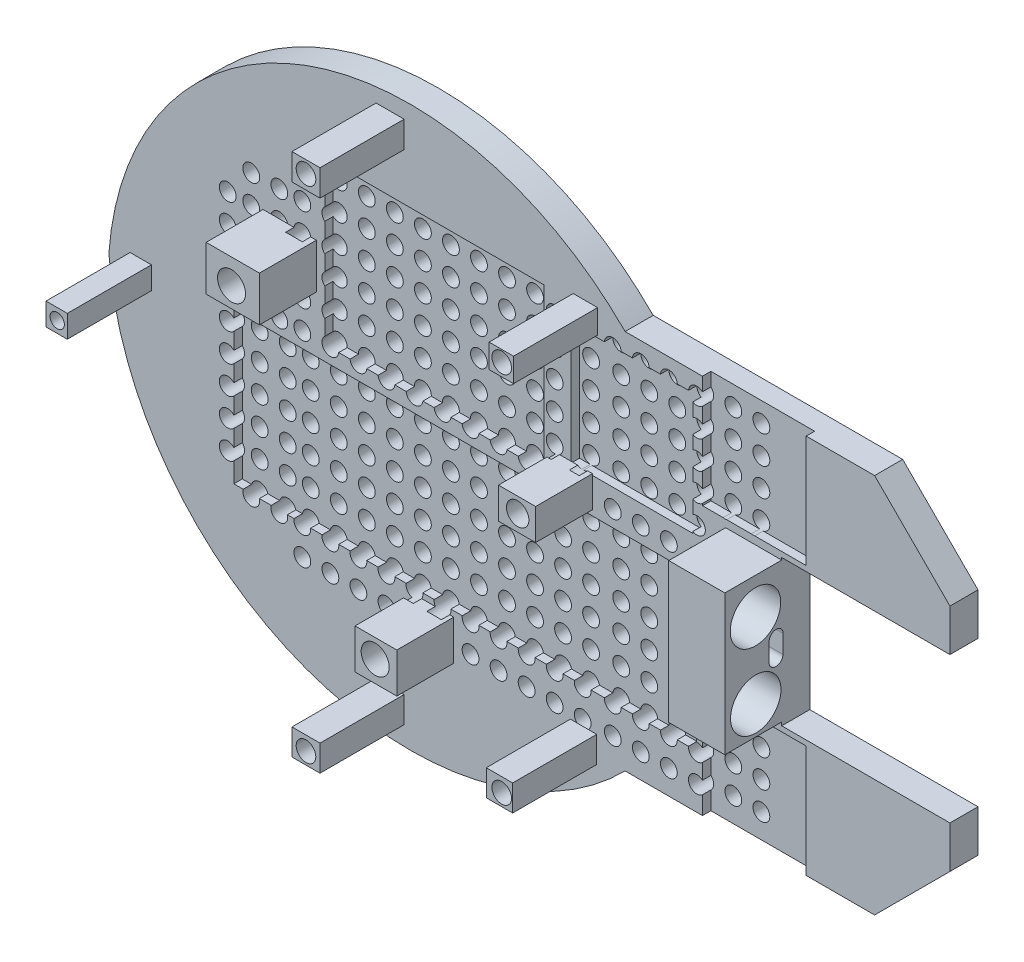
SolidWorks part; units mm, degrees
ref_plane "Front Plane" through (0, 0, 0) normal (0, 0, 1) x (1, 0, 0)
ref_plane "Top Plane" through (0, 0, 0) normal (0, 1, 0) x (1, 0, 0)
ref_plane "Right Plane" through (0, 0, 0) normal (1, 0, 0) x (0, 0, -1)
sketch "Sketch1" plane through (0, 0, 0) normal (0, 0, 1) x (1, 0, 0)
  line L1 (0, 0) -> (0, -26)
  line L2 (0, 26) -> (60, 26)
  line L3 (0, -26) -> (60, -26)
  line L4 (60, 26) -> (60, 41)
  line L5 (60, -26) -> (60, -41)
  line L6 (60, 41) -> (33.1299, 67.8701)
  line L7 (33.1299, 67.8701) -> (-55.8501, 67.8701)
  line L8 (60, -41) -> (33.1299, -67.8701)
  line L9 (33.1299, -67.8701) -> (-55.8501, -67.8701)
  line L10 (-55.8501, 67.8701) -> (-55.8501, 145.9436) construction
  line L11 (-55.8501, 145.9436) -> (-55.8501, -286.005) construction
  line L22 (0, 26) -> (0, 0)
  line L24 (-132.4482, 99.7954) -> (-270.7239, 99.7954) construction
  line L25 (-132.4482, 8.0579) -> (-132.4482, 125.9405) construction
  line L26 (-132.4482, -8.0579) -> (-132.4482, -125.1714) construction
  line L27 (-132.4482, -99.7954) -> (-270.7239, -99.7954) construction
  arc A7 (-240, 0) -> (-55.8501, 67.8701) centre (-132.4482, -8.0579) cw
  arc A8 (-55.8501, -67.8701) -> (-240, 0) centre (-132.4482, 8.0579) cw
  dimension "D11" = 199.5908
  dimension "D12" = 240
  dimension "D10" = 135.7401
  dimension "D1" = 26
  dimension "D2" = 26
  dimension "D3" = 60
  dimension "D4" = 15
  dimension "D5" = 15
  dimension "D6" = 135
  dimension "D7" = 38
  dimension "D8" = 38
  dimension "D9" = 135
  dimension "D15" = 88.98
  dimension "D16" = 88.98
extrude "Boss-Extrude1" add sketch "Sketch1" along normal blind 10 and the other way blind 0.01
sketch "Sketch3" plane through (0, 0, 10) normal (0, 0, 1) x (1, 0, 0)
  line L0 (33.1299, 67.8701) -> (-55.8501, 67.8701) construction
  line L1 (-28.273, 67.8701) -> (8.727, 67.8701)
  line L2 (-28.273, 67.8701) -> (-28.273, 27.8701)
  line L3 (-28.273, 27.8701) -> (8.727, 27.8701)
  line L4 (8.727, 67.8701) -> (8.727, 27.8701)
  dimension "D1" = 40
  dimension "D2" = 37
extrude "Cut-Extrude1" cut sketch "Sketch3" against normal blind 3 contours L2 L1 L4 L3
sketch "Sketch5" plane through (0, 0, 10) normal (0, 0, 1) x (1, 0, 0)
  line L0 (-55.8501, -67.8701) -> (33.1299, -67.8701) construction
  line L1 (-28.273, -27.8701) -> (8.727, -27.8701)
  line L2 (-28.273, -27.8701) -> (-28.273, -67.8701)
  line L3 (-28.273, -67.8701) -> (8.727, -67.8701)
  line L4 (8.727, -27.8701) -> (8.727, -67.8701)
extrude "Cut-Extrude3" cut sketch "Sketch5" against normal blind 3
sketch "Sketch7" plane through (0, 0, 10) normal (0, 0, 1) x (1, 0, 0)
  line L1 (-195.4131, 5.0562) -> (-30.4131, 5.0562)
  line L2 (-195.4131, 5.0562) -> (-195.4131, -48.9438)
  line L3 (-195.4131, -48.9438) -> (-30.4131, -48.9438)
  line L4 (-30.4131, 5.0562) -> (-30.4131, -48.9438)
  dimension "D1" = 54
  dimension "D2" = 165
extrude "Cut-Extrude4" cut sketch "Sketch7" against normal blind 3
sketch "Sketch8" plane through (0, 0, 10) normal (0, 0, 1) x (1, 0, 0)
  line L1 (-162.9927, 67.8133) -> (-84.7927, 67.8133)
  line L2 (-162.9927, 67.8133) -> (-162.9927, 10.3133)
  line L3 (-162.9927, 10.3133) -> (-84.7927, 10.3133)
  line L4 (-84.7927, 67.8133) -> (-84.7927, 10.3133)
  dimension "D1" = 78.2
  dimension "D2" = 57.5
extrude "Cut-Extrude5" cut sketch "Sketch8" against normal blind 3
sketch "Sketch9" plane through (0, 0, 10) normal (0, 0, 1) x (1, 0, 0)
  line L1 (-185, 41) -> (-166, 41)
  line L2 (-185, 41) -> (-185, 25)
  line L3 (-185, 25) -> (-166, 25)
  line L4 (-166, 41) -> (-166, 25)
  line L5 (-80.7317, 18.1542) -> (-67.493, 18.1542)
  line L6 (-80.7317, 18.1542) -> (-80.7317, 7.0108)
  line L7 (-80.7317, 7.0108) -> (-67.493, 7.0108)
  line L8 (-67.493, 18.1542) -> (-67.493, 7.0108)
  line L9 (-131.8867, -50.9252) -> (-116.9909, -50.9252)
  line L10 (-131.8867, -50.9252) -> (-131.8867, -65.1638)
  line L11 (-131.8867, -65.1638) -> (-116.9909, -65.1638)
  line L12 (-116.9909, -50.9252) -> (-116.9909, -65.1638)
  point P12 (0, 0)
  point P13 (0, 0)
  point P14 (0, 0)
  point P15 (0, 0)
  point P16 (0, 0)
  point P17 (0, 0)
  point P18 (0, 0)
  point P19 (0, 0)
  point P20 (0, 0)
extrude "Boss-Extrude2" add sketch "Sketch9" along normal blind 20.3
sketch "Sketch11" plane through (0, 0, -0.01) normal (0, 0, -1) x (-1, 0, 0)
  circle A0 centre (70.989, 60.5844) radius 3
  circle A1 centre (80.989, 60.5844) radius 3
  circle A2 centre (90.989, 60.5844) radius 3
  circle A3 centre (100.989, 60.5844) radius 3
  circle A4 centre (110.989, 60.5844) radius 3
  circle A5 centre (120.989, 60.5844) radius 3
  circle A6 centre (130.989, 60.5844) radius 3
  circle A7 centre (140.989, 60.5844) radius 3
  circle A8 centre (150.989, 60.5844) radius 3
  circle A9 centre (160.989, 60.5844) radius 3
  circle A10 centre (170.989, 60.5844) radius 3
  circle A11 centre (80.989, 50.5844) radius 3
  circle A12 centre (90.989, 50.5844) radius 3
  circle A13 centre (100.989, 50.5844) radius 3
  circle A14 centre (110.989, 50.5844) radius 3
  circle A15 centre (120.989, 50.5844) radius 3
  circle A16 centre (130.989, 50.5844) radius 3
  circle A17 centre (140.989, 50.5844) radius 3
  circle A18 centre (150.989, 50.5844) radius 3
  circle A19 centre (160.989, 50.5844) radius 3
  circle A20 centre (170.989, 50.5844) radius 3
  circle A21 centre (80.989, 40.5844) radius 3
  circle A22 centre (90.989, 40.5844) radius 3
  circle A23 centre (100.989, 40.5844) radius 3
  circle A24 centre (110.989, 40.5844) radius 3
  circle A25 centre (120.989, 40.5844) radius 3
  circle A26 centre (130.989, 40.5844) radius 3
  circle A27 centre (140.989, 40.5844) radius 3
  circle A28 centre (150.989, 40.5844) radius 3
  circle A29 centre (160.989, 40.5844) radius 3
  circle A30 centre (170.989, 40.5844) radius 3
  circle A31 centre (80.989, 30.5844) radius 3
  circle A32 centre (90.989, 30.5844) radius 3
  circle A33 centre (100.989, 30.5844) radius 3
  circle A34 centre (110.989, 30.5844) radius 3
  circle A35 centre (120.989, 30.5844) radius 3
  circle A36 centre (130.989, 30.5844) radius 3
  circle A37 centre (140.989, 30.5844) radius 3
  circle A38 centre (150.989, 30.5844) radius 3
  circle A39 centre (160.989, 30.5844) radius 3
  circle A40 centre (170.989, 30.5844) radius 3
  circle A41 centre (80.989, 20.5844) radius 3
  circle A42 centre (90.989, 20.5844) radius 3
  circle A43 centre (100.989, 20.5844) radius 3
  circle A44 centre (110.989, 20.5844) radius 3
  circle A45 centre (120.989, 20.5844) radius 3
  circle A46 centre (130.989, 20.5844) radius 3
  circle A47 centre (140.989, 20.5844) radius 3
  circle A48 centre (150.989, 20.5844) radius 3
  circle A49 centre (160.989, 20.5844) radius 3
  circle A50 centre (170.989, 20.5844) radius 3
  circle A51 centre (80.989, 10.5844) radius 3
  circle A52 centre (90.989, 10.5844) radius 3
  circle A53 centre (100.989, 10.5844) radius 3
  circle A54 centre (110.989, 10.5844) radius 3
  circle A55 centre (120.989, 10.5844) radius 3
  circle A56 centre (130.989, 10.5844) radius 3
  circle A57 centre (140.989, 10.5844) radius 3
  circle A58 centre (150.989, 10.5844) radius 3
  circle A59 centre (160.989, 10.5844) radius 3
  circle A60 centre (170.989, 10.5844) radius 3
  circle A61 centre (80.989, 0.5844) radius 3
  circle A62 centre (90.989, 0.5844) radius 3
  circle A63 centre (100.989, 0.5844) radius 3
  circle A64 centre (110.989, 0.5844) radius 3
  circle A65 centre (120.989, 0.5844) radius 3
  circle A66 centre (130.989, 0.5844) radius 3
  circle A67 centre (140.989, 0.5844) radius 3
  circle A68 centre (150.989, 0.5844) radius 3
  circle A69 centre (160.989, 0.5844) radius 3
  circle A70 centre (170.989, 0.5844) radius 3
  circle A71 centre (80.989, -9.4156) radius 3
  circle A72 centre (90.989, -9.4156) radius 3
  circle A73 centre (100.989, -9.4156) radius 3
  circle A74 centre (110.989, -9.4156) radius 3
  circle A75 centre (120.989, -9.4156) radius 3
  circle A76 centre (130.989, -9.4156) radius 3
  circle A77 centre (140.989, -9.4156) radius 3
  circle A78 centre (150.989, -9.4156) radius 3
  circle A79 centre (160.989, -9.4156) radius 3
  circle A80 centre (170.989, -9.4156) radius 3
  circle A81 centre (80.989, -19.4156) radius 3
  circle A82 centre (90.989, -19.4156) radius 3
  circle A83 centre (100.989, -19.4156) radius 3
  circle A84 centre (110.989, -19.4156) radius 3
  circle A85 centre (120.989, -19.4156) radius 3
  circle A86 centre (130.989, -19.4156) radius 3
  circle A87 centre (140.989, -19.4156) radius 3
  circle A88 centre (150.989, -19.4156) radius 3
  circle A89 centre (160.989, -19.4156) radius 3
  circle A90 centre (170.989, -19.4156) radius 3
  circle A91 centre (80.989, -29.4156) radius 3
  circle A92 centre (90.989, -29.4156) radius 3
  circle A93 centre (100.989, -29.4156) radius 3
  circle A94 centre (110.989, -29.4156) radius 3
  circle A95 centre (120.989, -29.4156) radius 3
  circle A96 centre (130.989, -29.4156) radius 3
  circle A97 centre (140.989, -29.4156) radius 3
  circle A98 centre (150.989, -29.4156) radius 3
  circle A99 centre (160.989, -29.4156) radius 3
  circle A100 centre (170.989, -29.4156) radius 3
  circle A101 centre (80.989, -39.4156) radius 3
  circle A102 centre (90.989, -39.4156) radius 3
  circle A103 centre (100.989, -39.4156) radius 3
  circle A104 centre (110.989, -39.4156) radius 3
  circle A105 centre (120.989, -39.4156) radius 3
  circle A106 centre (130.989, -39.4156) radius 3
  circle A107 centre (140.989, -39.4156) radius 3
  circle A108 centre (150.989, -39.4156) radius 3
  circle A109 centre (160.989, -39.4156) radius 3
  circle A110 centre (170.989, -39.4156) radius 3
  circle A111 centre (80.989, -49.4156) radius 3
  circle A112 centre (90.989, -49.4156) radius 3
  circle A113 centre (100.989, -49.4156) radius 3
  circle A114 centre (110.989, -49.4156) radius 3
  circle A115 centre (120.989, -49.4156) radius 3
  circle A116 centre (130.989, -49.4156) radius 3
  circle A117 centre (140.989, -49.4156) radius 3
  circle A118 centre (150.989, -49.4156) radius 3
  circle A119 centre (160.989, -49.4156) radius 3
  circle A120 centre (170.989, -49.4156) radius 3
  circle A121 centre (80.989, -59.4156) radius 3
  circle A122 centre (90.989, -59.4156) radius 3
  circle A123 centre (100.989, -59.4156) radius 3
  circle A124 centre (110.989, -59.4156) radius 3
  circle A125 centre (120.989, -59.4156) radius 3
  circle A126 centre (130.989, -59.4156) radius 3
  circle A127 centre (140.989, -59.4156) radius 3
  circle A128 centre (150.989, -59.4156) radius 3
  circle A129 centre (160.989, -59.4156) radius 3
  circle A130 centre (170.989, -59.4156) radius 3
  circle A131 centre (70.989, 50.5844) radius 3
  circle A132 centre (70.989, 40.5844) radius 3
  circle A133 centre (70.989, 30.5844) radius 3
  circle A134 centre (70.989, 20.5844) radius 3
  circle A135 centre (70.989, 10.5844) radius 3
  circle A136 centre (70.989, 0.5844) radius 3
  circle A137 centre (70.989, -9.4156) radius 3
  circle A138 centre (70.989, -19.4156) radius 3
  circle A139 centre (70.989, -29.4156) radius 3
  circle A140 centre (70.989, -39.4156) radius 3
  circle A141 centre (70.989, -49.4156) radius 3
  circle A142 centre (70.989, -59.4156) radius 3
  dimension "D1" = 11
  dimension "D2" = 13
extrude "Cut-Extrude12" cut sketch "Sketch11" against normal blind 13
sketch "Sketch12" plane through (0, 0, -0.01) normal (0, 0, -1) x (-1, 0, 0)
  circle A0 centre (179.2029, 50.2603) radius 3
  circle A1 centre (189.2029, 50.2603) radius 3
  circle A2 centre (189.2029, 40.2603) radius 3
  circle A3 centre (189.2029, 30.2603) radius 3
  circle A4 centre (189.2029, 20.2603) radius 3
  circle A5 centre (189.2029, 10.2603) radius 3
  circle A6 centre (189.2029, 0.2603) radius 3
  circle A7 centre (189.2029, -9.7397) radius 3
  circle A8 centre (189.2029, -19.7397) radius 3
  circle A9 centre (189.2029, -29.7397) radius 3
  circle A10 centre (189.2029, -39.7397) radius 3
  circle A11 centre (189.2029, -49.7397) radius 3
  circle A12 centre (179.2029, 40.2603) radius 3
  circle A13 centre (179.2029, 30.2603) radius 3
  circle A14 centre (179.2029, 20.2603) radius 3
  circle A15 centre (179.2029, 10.2603) radius 3
  circle A16 centre (179.2029, 0.2603) radius 3
  circle A17 centre (179.2029, -9.7397) radius 3
  circle A18 centre (179.2029, -19.7397) radius 3
  circle A19 centre (179.2029, -29.7397) radius 3
  circle A20 centre (179.2029, -39.7397) radius 3
  circle A21 centre (179.2029, -49.7397) radius 3
  dimension "D1" = 2
  dimension "D2" = 11
extrude "Cut-Extrude13" cut sketch "Sketch12" against normal up to surface (10.01 mm away) up to face at (-153.989, -59.4156, 10)
sketch "Sketch13" plane through (0, 0, -0.01) normal (0, 0, -1) x (-1, 0, 0)
  circle A0 centre (197.6037, 40.2121) radius 3
  circle A1 centre (197.6037, 30.2121) radius 3
  circle A2 centre (197.6037, 20.2121) radius 3
  circle A3 centre (197.6037, 10.2121) radius 3
  circle A4 centre (197.6037, 0.2121) radius 3
  circle A5 centre (197.6037, -9.7879) radius 3
  circle A6 centre (197.6037, -19.7879) radius 3
  circle A7 centre (197.6037, -29.7879) radius 3
  circle A8 centre (197.6037, -39.7879) radius 3
  dimension "D1" = 9
extrude "Cut-Extrude14" cut sketch "Sketch13" against normal up to surface (10.01 mm away) up to face at (-182.2029, 20.2603, 10)
sketch "Sketch14" plane through (0, 0, -0.01) normal (0, 0, -1) x (-1, 0, 0)
  circle A0 centre (60.2552, 60.8035) radius 3
  circle A1 centre (50.2552, 60.8035) radius 3
  circle A2 centre (40.2552, 60.8035) radius 3
  circle A3 centre (30.2552, 60.8035) radius 3
  circle A4 centre (20.2552, 60.8035) radius 3
  circle A5 centre (10.2552, 60.8035) radius 3
  circle A6 centre (50.2552, 50.8035) radius 3
  circle A7 centre (40.2552, 50.8035) radius 3
  circle A8 centre (30.2552, 50.8035) radius 3
  circle A9 centre (20.2552, 50.8035) radius 3
  circle A10 centre (10.2552, 50.8035) radius 3
  circle A11 centre (50.2552, 40.8035) radius 3
  circle A12 centre (40.2552, 40.8035) radius 3
  circle A13 centre (30.2552, 40.8035) radius 3
  circle A14 centre (20.2552, 40.8035) radius 3
  circle A15 centre (10.2552, 40.8035) radius 3
  circle A16 centre (50.2552, 30.8035) radius 3
  circle A17 centre (40.2552, 30.8035) radius 3
  circle A18 centre (30.2552, 30.8035) radius 3
  circle A19 centre (20.2552, 30.8035) radius 3
  circle A20 centre (10.2552, 30.8035) radius 3
  circle A21 centre (50.2552, 20.8035) radius 3
  circle A22 centre (40.2552, 20.8035) radius 3
  circle A23 centre (30.2552, 20.8035) radius 3
  circle A24 centre (20.2552, 20.8035) radius 3
  circle A25 centre (10.2552, 20.8035) radius 3
  circle A26 centre (50.2552, 10.8035) radius 3
  circle A27 centre (40.2552, 10.8035) radius 3
  circle A28 centre (30.2552, 10.8035) radius 3
  circle A29 centre (20.2552, 10.8035) radius 3
  circle A30 centre (10.2552, 10.8035) radius 3
  circle A31 centre (50.2552, 0.8035) radius 3
  circle A32 centre (40.2552, 0.8035) radius 3
  circle A33 centre (30.2552, 0.8035) radius 3
  circle A34 centre (20.2552, 0.8035) radius 3
  circle A35 centre (10.2552, 0.8035) radius 3
  circle A36 centre (50.2552, -9.1965) radius 3
  circle A37 centre (40.2552, -9.1965) radius 3
  circle A38 centre (30.2552, -9.1965) radius 3
  circle A39 centre (20.2552, -9.1965) radius 3
  circle A40 centre (10.2552, -9.1965) radius 3
  circle A41 centre (50.2552, -19.1965) radius 3
  circle A42 centre (40.2552, -19.1965) radius 3
  circle A43 centre (30.2552, -19.1965) radius 3
  circle A44 centre (20.2552, -19.1965) radius 3
  circle A45 centre (10.2552, -19.1965) radius 3
  circle A46 centre (50.2552, -29.1965) radius 3
  circle A47 centre (40.2552, -29.1965) radius 3
  circle A48 centre (30.2552, -29.1965) radius 3
  circle A49 centre (20.2552, -29.1965) radius 3
  circle A50 centre (10.2552, -29.1965) radius 3
  circle A51 centre (50.2552, -39.1965) radius 3
  circle A52 centre (40.2552, -39.1965) radius 3
  circle A53 centre (30.2552, -39.1965) radius 3
  circle A54 centre (20.2552, -39.1965) radius 3
  circle A55 centre (10.2552, -39.1965) radius 3
  circle A56 centre (50.2552, -49.1965) radius 3
  circle A57 centre (40.2552, -49.1965) radius 3
  circle A58 centre (30.2552, -49.1965) radius 3
  circle A59 centre (20.2552, -49.1965) radius 3
  circle A60 centre (10.2552, -49.1965) radius 3
  circle A61 centre (50.2552, -59.1965) radius 3
  circle A62 centre (40.2552, -59.1965) radius 3
  circle A63 centre (30.2552, -59.1965) radius 3
  circle A64 centre (20.2552, -59.1965) radius 3
  circle A65 centre (10.2552, -59.1965) radius 3
  circle A66 centre (60.2552, 50.8035) radius 3
  circle A67 centre (60.2552, 40.8035) radius 3
  circle A68 centre (60.2552, 30.8035) radius 3
  circle A69 centre (60.2552, 20.8035) radius 3
  circle A70 centre (60.2552, 10.8035) radius 3
  circle A71 centre (60.2552, 0.8035) radius 3
  circle A72 centre (60.2552, -9.1965) radius 3
  circle A73 centre (60.2552, -19.1965) radius 3
  circle A74 centre (60.2552, -29.1965) radius 3
  circle A75 centre (60.2552, -39.1965) radius 3
  circle A76 centre (60.2552, -49.1965) radius 3
  circle A77 centre (60.2552, -59.1965) radius 3
  dimension "D1" = 6
  dimension "D2" = 13
extrude "Cut-Extrude16" cut sketch "Sketch14" against normal up to surface (10.01 mm away) up to face at (-200.6037, 40.2121, 10)
sketch "Sketch15" plane through (0, 0, 10) normal (0, 0, 1) x (1, 0, 0)
  line L0 (0, -26) -> (0, 26) construction
  line L1 (-20, 25.2016) -> (0, 25.2016)
  line L2 (-20, 25.2016) -> (-20, -24.7984)
  line L3 (-20, -24.7984) -> (0, -24.7984)
  line L4 (0, 25.2016) -> (0, -24.7984)
  dimension "D1" = 50
  dimension "D2" = 20
extrude "Boss-Extrude3" add sketch "Sketch15" along normal blind 20.3
sketch "Sketch4" plane through (0, 0, 7) normal (0, 0, 1) x (1, 0, 0)
  line L1 (-28.3661, -27.8728) -> (8.6339, -27.8728)
  line L2 (-28.3661, -27.8728) -> (-28.3661, -67.8728)
  line L3 (-28.3661, -67.8728) -> (8.6339, -67.8728)
  line L4 (8.6339, -27.8728) -> (8.6339, -67.8728)
  dimension "D1" = 40
  dimension "D2" = 37
sketch "Sketch16" plane through (0, 0, 10) normal (0, 0, 1) x (1, 0, 0)
  line L1 (-232.4208, 4) -> (-224.8235, 4)
  line L2 (-232.4208, 4) -> (-232.4208, -4)
  line L3 (-232.4208, -4) -> (-224.8235, -4)
  line L4 (-224.8235, 4) -> (-224.8235, -4)
  line L9 (-134.6881, 94.0493) -> (-144.6881, 94.0493)
  line L10 (-134.6881, 94.0493) -> (-134.6881, 84.6493)
  line L11 (-134.6881, 84.6493) -> (-144.6881, 84.6493)
  line L12 (-144.6881, 94.0493) -> (-144.6881, 84.6493)
  line L13 (-65.6779, 70.3488) -> (-74.3779, 70.3488)
  line L14 (-65.6779, 70.3488) -> (-65.6779, 61.8488)
  line L15 (-65.6779, 61.8488) -> (-74.3779, 61.8488)
  line L16 (-74.3779, 70.3488) -> (-74.3779, 61.8488)
  line L17 (-65.9779, -61.6233) -> (-75.3779, -61.6233)
  line L18 (-65.9779, -61.6233) -> (-65.9779, -70.9233)
  line L19 (-65.9779, -70.9233) -> (-75.3779, -70.9233)
  line L20 (-75.3779, -61.6233) -> (-75.3779, -70.9233)
  line L21 (-134.6881, -83.6815) -> (-144.6881, -83.6815)
  line L22 (-134.6881, -83.6815) -> (-134.6881, -92.9815)
  line L23 (-134.6881, -92.9815) -> (-144.6881, -92.9815)
  line L24 (-144.6881, -83.6815) -> (-144.6881, -92.9815)
extrude "Boss-Extrude4" add sketch "Sketch16" along normal blind 30
sketch "Sketch17" plane through (0, 0, 0) normal (0, 0, 1) x (1, 0, 0)
  circle A1 centre (-228.4208, 0) radius 2.55
  circle A2 centre (-139.6881, 89.6493) radius 3.5
  circle A3 centre (-69.8779, 66.3488) radius 3.5
  circle A4 centre (-69.8779, -66.6233) radius 3.5
  circle A5 centre (-139.6881, -88.6815) radius 3.5
extrude "Cut-Extrude17" cut sketch "Sketch17" along normal through all
sketch "Sketch18" plane through (0, 0, 10) normal (0, 0, 1) x (1, 0, 0)
  line L1 (-75.1245, 61) -> (-31.7245, 61)
  line L2 (-75.1245, 61) -> (-75.1245, 17.6)
  line L3 (-75.1245, 17.6) -> (-31.7245, 17.6)
  line L4 (-31.7245, 61) -> (-31.7245, 17.6)
  dimension "D1" = 43.4
  dimension "43.4" = 43.4
extrude "Cut-Extrude18" cut sketch "Sketch18" against normal blind 3
sketch "Sketch20" plane through (0, 0, 0) normal (0, 0, 1) x (1, 0, 0)
  circle A0 centre (-175.9471, 32.1121) radius 5
  circle A1 centre (-124.7094, -57.6129) radius 5
  circle A2 centre (-73.8879, 12.7504) radius 4
  point P6 (0, 0)
  point P7 (0, 0)
  point P8 (0, 0)
extrude "Cut-Extrude20" cut sketch "Sketch20" along normal through all
sketch "Sketch21" plane through (0, 0, 0) normal (1, 0, 0) x (0, 0, -1)
  line L0 (-3.8276, 29.0855) -> (-3.8276, -37.1575) construction
  line L1 (-6.4886, 28.3852) -> (-6.4886, -37.2976) construction
  line L2 (-5.0881, 28.1051) -> (-5.0881, -37.5777) construction
  line L3 (-11.99, 2.3019) -> (-12.0559, -4.1532) construction
  line L4 (-9.4916, 2.2764) -> (-9.5574, -4.1787)
  line L5 (-14.4885, 2.3274) -> (-14.5544, -4.1277)
  circle A0 centre (-19.3619, 12.3718) radius 9
  circle A1 centre (-19.2654, -14.6282) radius 9
  arc A2 (-9.4916, 2.2764) -> (-14.4885, 2.3274) centre (-11.99, 2.3019) ccw
  arc A3 (-14.5544, -4.1277) -> (-9.5574, -4.1787) centre (-12.0559, -4.1532) ccw
  point P12 (-12.023, -0.9256)
  dimension "D1" = 18
  dimension "D2" = 18
  dimension "D3" = 27
extrude "Cut-Extrude21" cut sketch "Sketch21" against normal up to surface (20 mm away) up to face at (-20, 0.6315, 12.9)
